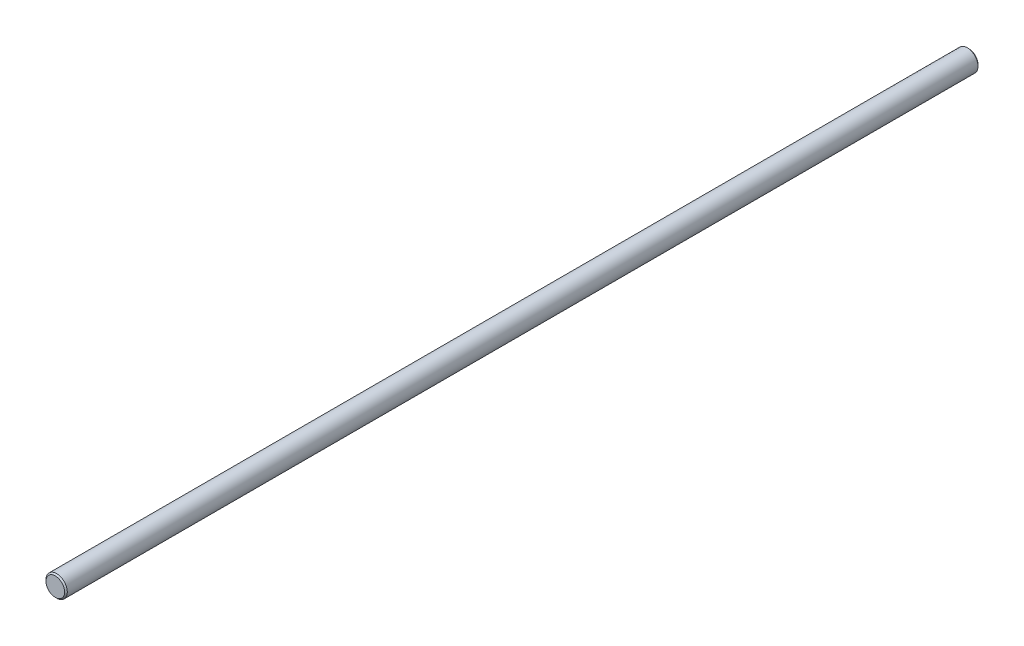
SolidWorks part; units mm, degrees
ref_plane "Front Plane" through (0, 0, 0) normal (0, 0, 1) x (1, 0, 0)
ref_plane "Top Plane" through (0, 0, 0) normal (0, 1, 0) x (1, 0, 0)
ref_plane "Right Plane" through (0, 0, 0) normal (1, 0, 0) x (0, 0, -1)
sketch "Sketch1" plane through (0, 0, 0) normal (0, 0, 1) x (1, 0, 0)
  circle A0 centre (0, 0) radius 4
  dimension "D1" = 8
extrude "Boss-Extrude1" add sketch "Sketch1" along normal blind 342.9
chamfer "Chamfer1" distance 0.5 angle 45 2 edges at (4, 0, 0) (4, 0, 342.9)
